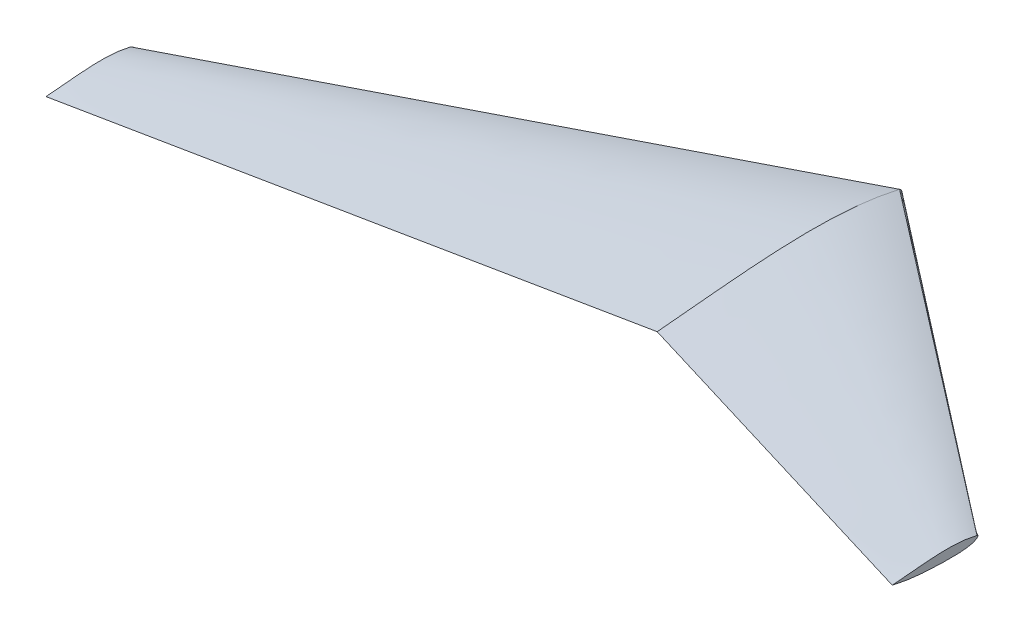
SolidWorks part; units mm, degrees
ref_plane "Front Plane" through (0, 0, 0) normal (0, 0, 1) x (1, 0, 0)
ref_plane "Top Plane" through (0, 0, 0) normal (0, 1, 0) x (1, 0, 0)
ref_plane "Right Plane" through (0, 0, 0) normal (1, 0, 0) x (0, 0, -1)
sketch "Sketch2" plane through (0, 0, 0) normal (0, 1, 0) x (1, 0, 0)
  line L0 (0, -5194.446) -> (0, 1731.482)
  line L1 (0, 0) -> (-18096.1342, 0) construction
  line L2 (0, 0) -> (-22098, -13277.818) construction
  line L3 (-22098, -15095.8741) -> (-22098, -12671.7993)
  line L4 (-22098, -12671.7993) -> (0, 1731.482)
  line L5 (-22098, -15095.8741) -> (0, -5194.446)
  line L6 (-9275.7037, -4314.3398) -> (-9275.7037, -5573.4051) construction
  line L7 (-9275.7037, -5573.4051) -> (-9275.7037, -9350.601) construction
  line L8 (-9275.7037, -5573.4051) -> (0, -5573.4051) construction
  line L9 (0, 346.2964) -> (-6827.52, -3825.6374)
  line L10 (0, -29565.6) -> (-7316.724, -34881.5112) construction
  line L11 (0, -29565.6) -> (-8167.6786, -29565.6) construction
  line L12 (0, -28507.0982) -> (0, -32741.1055)
  line L13 (-7316.724, -35992.9378) -> (-7316.724, -34511.0356)
  line L14 (-7316.724, -34511.0356) -> (0, -28507.0982)
  line L15 (0, -32741.1055) -> (-7316.724, -35992.9378)
  line L16 (-2399.2704, -30475.8849) -> (-2399.2704, -31308.772) construction
  line L17 (-2399.2704, -31308.772) -> (-2399.2704, -33807.4331) construction
  line L18 (-2399.2704, -31308.772) -> (0, -31308.772) construction
  line L19 (-6827.52, -3825.6374) -> (-6827.52, -6593.1427)
  line L20 (-6827.52, -6593.1427) -> (0, -3116.6676)
  line L21 (0, 346.2964) -> (0, -3116.6676) construction
  line L22 (0, -3116.6676) -> (0, 346.2964) construction
  line L23 (0, 346.2964) -> (0, -1385.1856) construction
  line L24 (0, 346.2964) -> (0, -3116.6676) construction
  line L25 (0, -1385.1856) -> (-6827.52, -5209.39) construction
  line L26 (0, 346.2964) -> (-22098, -13156.6142) construction
  line L27 (-3160.776, -1585.0854) -> (-3160.776, -3155.5874) construction
  line L28 (-3160.776, -3155.5874) -> (-3160.776, -4726.0893) construction
  line L29 (-3160.776, -3155.5874) -> (0, -3155.5874) construction
  dimension "Wing Sweep" = 31
  dimension "Half Span" = 22098
  dimension "Wing Root" = 6925.928
  dimension "D4" = 1731.482
  dimension "Wing Tip" = 2424.0748
  dimension "D6" = 606.0187
  dimension "Wing YBar" = 9275.7037
  dimension "Tail Sweep" = 36
  dimension "Tail Root" = 4234.0073
  dimension "D10" = 1058.5018
  dimension "Tail Tip" = 1481.9022
  dimension "D12" = 370.4756
  dimension "D13" = 7316.724
  dimension "Tail Ybar" = 2399.2704
  dimension "First Spar" = 1385.1856
  dimension "Second Spar" = 4848.1496
  dimension "Fuel Tip" = 2767.5053
  dimension "Tip Spar" = 484.815
  dimension "Fuel Ybar" = 3160.776
  dimension "Fuel Tank Length" = 6827.52
  dimension "Tail Arm" = 29565.6
sketch "Sketch4" plane through (0, 0, 0) normal (0, 1, 0) x (1, 0, 0)
  line L0 (0, 18200.9949) -> (0, -34834.2051) construction
  line L1 (-2240.28, 18200.9949) -> (2240.28, 18200.9949) construction
  line L2 (-2240.28, 11480.1549) -> (-2240.28, -25873.0851)
  line L3 (-2240.28, -34834.2051) -> (2240.28, -34834.2051) construction
  line L4 (2240.28, 11480.1549) -> (2240.28, -25873.0851)
  line L5 (0, -5194.446) -> (0, 1731.482) construction
  line L6 (-9275.7037, -5573.4051) -> (0, -5573.4051) construction
  line L7 (-2399.2704, -31308.772) -> (0, -31308.772) construction
  line L8 (0, 0) -> (-22098, -13277.818) construction
  line L9 (-22098, -12671.7993) -> (0, 1731.482) construction
  line L10 (-8451.85, 1616.4392) -> (-6132.83, 1616.4392)
  line L11 (-8451.85, 1616.4392) -> (-8451.85, -3941.0808)
  line L12 (-8451.85, -3941.0808) -> (-6132.83, -3941.0808)
  line L13 (-6132.83, 1616.4392) -> (-6132.83, -3941.0808)
  line L14 (2240.28, 11480.1549) -> (-2240.28, 11480.1549)
  arc A0 (-2240.28, -25873.0851) -> (2240.28, -25873.0851) centre (0, -25873.0851) ccw construction
  spline S0 degree 2 poles (-2240.28, 11480.1549) (-2010.8321, 15064.3252) (0, 18200.9949) knots 0 0 0 1 1 1 construction
  spline S1 degree 2 poles (2240.28, 11480.1549) (2010.8321, 15064.3252) (0, 18200.9949) knots 0 0 0 1 1 1 construction
  spline S2 degree 3 poles (-2240.28, -25873.0851) (-2042.135, -27711.7659) (-2075.1921, -30173.7144) (-919.8513, -32825.3563) (0, -32741.1055) knots 0 0 0 0 0.711043 1 1 1 1 construction
  spline S3 degree 3 poles (2240.28, -25873.0851) (2042.135, -27711.7659) (2075.1921, -30173.7144) (919.8513, -32825.3563) (0, -32741.1055) knots 0 0 0 0 0.711043 1 1 1 1 construction
  spline S4 degree 2 poles (-2240.28, -25873.0851) (-2027.1744, -27637.7456) (0, -27753.3552) knots 0 0 0 1 1 1
  spline S5 degree 2 poles (2240.28, -25873.0851) (2027.1744, -27637.7456) (0, -27753.3552) knots 0 0 0 1 1 1
  point P6 (0, 11480.1549)
  point P7 (0, -25873.0851)
  point P8 (0, -5573.4051)
  point P15 (0, -28113.3651)
  point P28 (-7292.34, 1616.4392)
  point P29 (-7292.34, -3021.6008)
  point P35 (-7292.34, -4381.6799)
  point P44 (-7292.34, -606.5688)
  dimension "Fuse Length" = 53035.2
  dimension "Fuse Dia" = 4480.56
  dimension "D3" = 6720.84
  dimension "D4" = 8961.12
  dimension "D6" = 7292.34
  dimension "Engine Dia" = 2319.02
  dimension "Engine Length" = 5557.52
  dimension "D9" = 4638.04
  dimension "D10" = 2223.008
  dimension "D11" = 4966.8362
  dimension "D2" = 23774.4
ref_plane "Plane1" through (0, 609.6, 0) normal (0, 1, 0) x (1, 0, 0)
sketch "Sketch10" plane through (0, 0, 0) normal (0, 1, 0) x (1, 0, 0)
  line L0 (-22098, -12671.7993) -> (-2240.28, 271.2873)
  line L1 (-2240.28, 11480.1549) -> (-2240.28, -25873.0851) construction
  line L2 (-22098, -12671.7993) -> (-22098, -15095.8741)
  line L3 (-22098, -15095.8741) -> (-7292.34, -8461.9172)
  line L4 (-7292.34, -8461.9172) -> (-2240.28, -8461.9172)
  line L5 (-22098, -15095.8741) -> (0, -5194.446) construction
  line L6 (-22098, -12671.7993) -> (0, 1731.482) construction
  line L7 (-2240.28, -8461.9172) -> (-2240.28, 271.2873) construction
  line L9 (0, 271.2873) -> (0, -8461.9172)
  line L10 (0, -8461.9172) -> (-2240.28, -8461.9172)
  line L11 (0, -5194.446) -> (0, 1731.482) construction
  line L12 (-2240.28, 271.2873) -> (0, 1731.482)
  line L13 (0, 1731.482) -> (0, 271.2873)
ref_plane "Plane4" through (13979.3336, 0, 17035.9747) normal (0.6343, 0, 0.773) x (0.773, 0, -0.6343)
ref_plane "Plane2" through (-7316.724, 0, 0) normal (1, 0, 0) x (0, 0, -1)
sketch "Sketch11" plane through (0, 0, 0) normal (1, 0, 0) x (0, 0, -1)
  line L0 (-31394.1382, -352.4096) -> (-30857.4716, -352.4096) construction
  line L1 (-28507.0982, 0) -> (-32741.1055, 0) construction
  spline S0 degree 3 poles (-32741.1055, 0) (-32087.6108, 58.4964) (-30694.3744, 215.6293) (-29283.3414, 206.7354) (-28550.6224, 37.3552) knots 0 0 0 0 0.467766 1 1 1 1
  spline S1 degree 3 poles (-32741.1055, 0) (-31699.0664, -259.8493) (-30612.0325, -286.5067) (-29544.5629, -281.2625) knots 0 0 0 0 1 1 1 1
  spline S2 degree 3 poles (-29544.5629, -281.2625) (-29299.6404, -272.429) (-28941.2534, -250.6732) (-28603.1064, -121.0879) (-28470.9045, -13.0597) (-28550.6224, 37.3552) knots 0 0 0 0 0.658433 0.851821 1 1 1 1
sketch "Sketch12" plane through (13979.3336, 0, 17035.9747) normal (0.6343, 0, 0.773) x (0.773, 0, -0.6343)
  line L0 (-18081.2415, -230.124) -> (-27548.1365, 1399.6081)
  line L1 (-18081.2415, 230.124) -> (-27548.7376, 1560.6938)
  line L2 (-18081.2415, 230.124) -> (-18081.2415, -230.124) construction
  line L3 (-27548.7376, 1560.6938) -> (-27548.1365, 1399.6081) construction
  line L4 (-18083.3748, 0) -> (-20769.202, 0) construction
  line L6 (-27548.7376, 1560.6938) -> (-22696.9304, 1560.6938) construction
  point P1 (-18081.2415, 0)
  dimension "D1" = 8
  dimension "D2" = 460.248
  dimension "D3" = 161.0868
sketch "Sketch13" plane through (-7316.724, 0, 0) normal (1, 0, 0) x (0, 0, -1)
  line L0 (-34331.3091, -72.3608) -> (-33794.6424, -72.3608) construction
  spline S0 degree 2 poles (-34510.9313, 1487.8287) (-34516.9128, 1498.8726) (-34529.2879, 1500.886) knots 0 0 0 1 1 1
  spline S1 degree 3 poles (-34510.9313, 1487.8287) (-34514.5724, 1474.6857) (-34536.1147, 1454.9522) (-34589.7444, 1427.7912) (-34673.4646, 1407.2052) (-34806.5245, 1391.6785) (-34974.1909, 1387.9883) (-35379.9014, 1394.6932) (-35723.092, 1421.5306) (-35992.8335, 1487.8287) knots 0 0 0 0 0.026229 0.055394 0.119138 0.195327 0.321011 0.45098 1 1 1 1
  spline S2 degree 3 poles (-35992.8335, 1487.8287) (-35968.1105, 1492.8498) (-35903.0682, 1497.5537) (-35767.7366, 1510.0376) (-35566.0534, 1525.4754) (-35143.3506, 1565.9543) (-34787.565, 1564.8464) (-34529.2879, 1500.886) knots 0 0 0 0 0.051367 0.133023 0.277496 0.464226 1 1 1 1
loft "Loft1" add profiles "Sketch13", "Sketch11" connector at (-7316.724, 1487.8287, 35992.8335) connector at (0, 0, 32741.1055)
mirror "Mirror1" about plane through (0, 0, 0) normal (1, 0, 0) of bodies 130
equation "\"D6@Sketch2\" = \"Wing Tip@Sketch2\" / 4"
equation "\"D4@Sketch2\" = \"Wing Root@Sketch2\" / 4"
equation "\"D10@Sketch2\" = \"Tail Root@Sketch2\" / 4"
equation "\"D12@Sketch2\" = \"Tail Tip@Sketch2\" / 4"
equation "\"D13@Sketch2\"=48.01/2"
equation "\"First Spar@Sketch2\"=0.2 * \"Wing Root@Sketch2\""
equation "\"Second Spar@Sketch2\"   = 0.7 * \"Wing Root@Sketch2\""
equation "\"Tip Spar@Sketch2\"=0.2 * \"Wing Tip@Sketch2\""
equation "\"D3@Sketch4\" = 1.5 * \"Fuse Dia@Sketch4\""
equation "\"D4@Sketch4\" = 2 * \"Fuse Dia@Sketch4\""
equation "\"D6@Sketch4\" = 0.33 * \"Half Span@Sketch2\""
equation "\"D9@Sketch4\" = 2 * \"Engine Dia@Sketch4\""
equation "\"D10@Sketch4\" = 0.40 * \"Engine Length@Sketch4\""
equation "\"D3@Sketch12\"=0.35*\"D2@Sketch12\""
